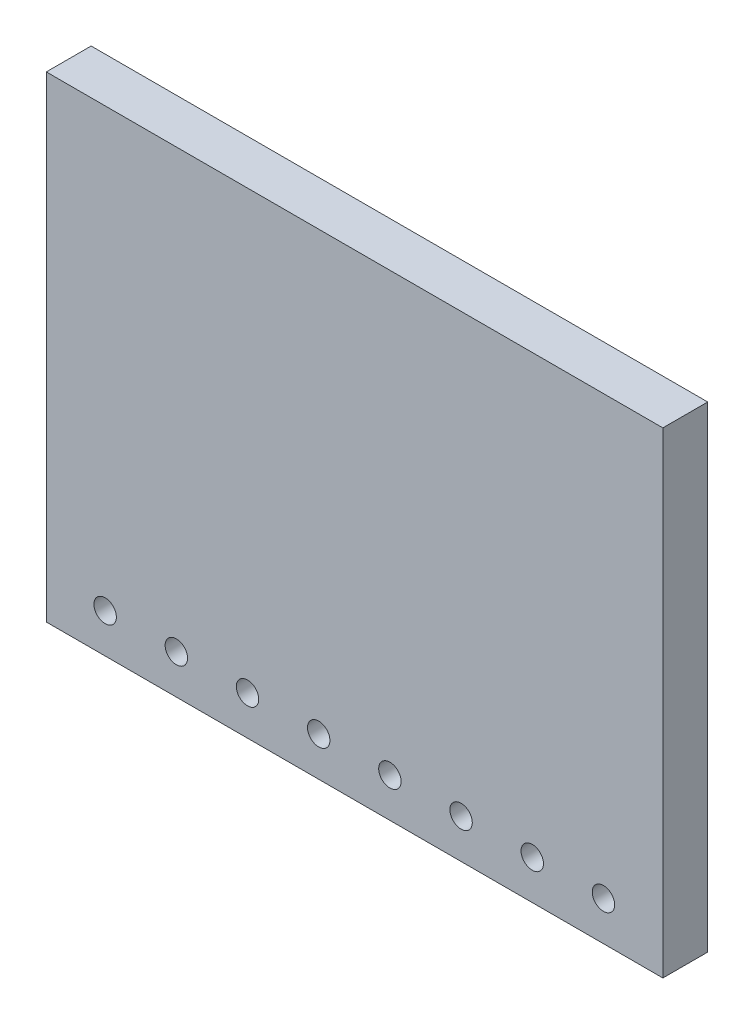
SolidWorks part; units mm, degrees
ref_plane "Front Plane" through (0, 0, 0) normal (0, 0, 1) x (1, 0, 0)
ref_plane "Top Plane" through (0, 0, 0) normal (0, 1, 0) x (1, 0, 0)
ref_plane "Right Plane" through (0, 0, 0) normal (1, 0, 0) x (0, 0, -1)
sketch "Sketch1" plane through (0, 0, 0) normal (0, 0, 1) x (1, 0, 0)
  line L1 (11, 8.5) -> (-11, 8.5)
  line L2 (11, 8.5) -> (11, -8.5)
  line L3 (11, -8.5) -> (-11, -8.5)
  line L4 (-11, 8.5) -> (-11, -8.5)
  line L5 (11, 8.5) -> (-11, -8.5) construction
  line L6 (11, -8.5) -> (-11, 8.5) construction
  point P0 (0, 0)
  dimension "D1" = 22
  dimension "D2" = 17
extrude "Boss-Extrude1" add sketch "Sketch1" along normal blind 1.6
sketch "Sketch2" plane through (0, 0, 1.6) normal (0, 0, 1) x (1, 0, 0)
  line L0 (-11, 8.5) -> (-11, -8.5) construction
  line L2 (-11, -8.5) -> (11, -8.5) construction
  circle A0 centre (-8.9, -7.1) radius 0.4
  circle A1 centre (-6.36, -7.1) radius 0.4
  circle A2 centre (-3.82, -7.1) radius 0.4
  circle A3 centre (-1.28, -7.1) radius 0.4
  circle A4 centre (1.26, -7.1) radius 0.4
  circle A5 centre (3.8, -7.1) radius 0.4
  circle A6 centre (6.34, -7.1) radius 0.4
  circle A7 centre (8.88, -7.1) radius 0.4
  point P4 (-7.6859, -7.4801)
  point P7 (0, 0)
  point P8 (0, 0)
  point P11 (-4.457, -7.4801)
  point P14 (-2.4218, -7.4801)
  point P17 (0, -7.4801)
  point P20 (2.195, -7.4801)
  point P23 (4.1363, -7.4801)
  point P26 (6.1738, -7.4801)
  point P27 (0, 0)
  point P28 (0, 0)
  point P29 (0, 0)
  point P30 (8.3709, -7.5588)
  point P31 (7.9707, -7.4801)
  point P36 (0, 0)
  dimension "D1" = 0.8
  dimension "D2" = 2.54
  dimension "D3" = 2.1
  dimension "D4" = 2.54
  dimension "D5" = 2.54
  dimension "D6" = 2.54
  dimension "D7" = 2.54
  dimension "D8" = 2.54
  dimension "D9" = 2.54
  dimension "D10" = 1.4
  dimension "D11" = 1.4
  dimension "D12" = 1.4
  dimension "D13" = 1.4
  dimension "D14" = 1.4
  dimension "D15" = 1.4
  dimension "D16" = 1.4
  dimension "D17" = 1.4
extrude "Cut-Extrude1" cut sketch "Sketch2" against normal up to next
